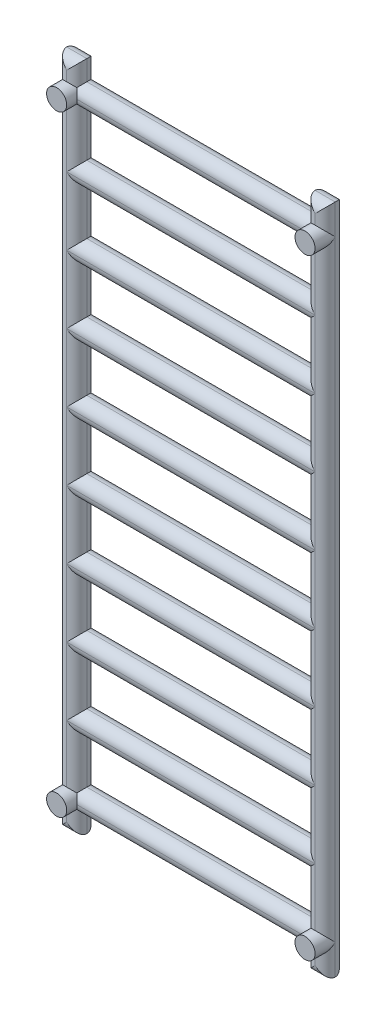
SolidWorks part; units mm, degrees
ref_plane "Спереди" through (0, 0, 0) normal (0, 0, 1) x (1, 0, 0)
ref_plane "Сверху" through (0, 0, 0) normal (0, 1, 0) x (1, 0, 0)
ref_plane "Справа" through (0, 0, 0) normal (1, 0, 0) x (0, 0, -1)
other "Configuration Table"
sketch "Эскиз2" plane through (0, 0, 0) normal (0, 1, 0) x (1, 0, 0)
  line L1 (-15, -15) -> (15, -15)
  line L2 (-15, -15) -> (-15, 15)
  line L3 (-15, 15) -> (15, 15)
  line L4 (15, -15) -> (15, 15)
  line L5 (-15, -15) -> (15, 15) construction
  line L6 (-15, 15) -> (15, -15) construction
  line L7 (355, 15) -> (385, 15)
  line L8 (355, 15) -> (355, -15)
  line L9 (355, -15) -> (385, -15)
  line L10 (385, 15) -> (385, -15)
  line L11 (355, 15) -> (385, -15) construction
  line L12 (355, -15) -> (385, 15) construction
  point P0 (0, 0)
  point P6 (370, 0)
  dimension "D1" = 30
  dimension "D2" = 400
extrude "Бобышка-Вытянуть1" add sketch "Эскиз2" along normal blind 1000
sketch "Эскиз3" plane through (15, 0, 0) normal (1, 0, 0) x (0, 0, -1)
  line L0 (-15, 1000) -> (-15, 0) construction
  line L1 (-15, 60) -> (15, 60)
  line L2 (-15, 60) -> (-15, 30)
  line L3 (-15, 30) -> (15, 30)
  line L4 (15, 60) -> (15, 30)
  line L5 (15, 1000) -> (15, 0) construction
  line L6 (15, 0) -> (15, 30) construction
extrude "Бобышка-Вытянуть2" add sketch "Эскиз3" along normal up to surface (340 mm away) up to face at (355, 500, 0)
pattern_linear "Линейный массив1" count 10 spacing 101.1111 along (0, 1, 0) of "Бобышка-Вытянуть2"
fillet "Скругление1" radius 15 96 edges at (355, 95.5556, -15) (185, 60, -15) (15, 95.5556, -15) (185, 131.1111, -15) (355, 196.6667, -15) (185, 161.1111, -15) (15, 196.6667, -15) (185, 232.2222, -15) (355, 297.7778, -15) (185, 262.2222, -15) (15, 297.7778, -15) (185, 333.3333, -15) (355, 398.8889, -15) (185, 363.3333, -15) (15, 398.8889, -15) (185, 434.4444, -15) (355, 500, -15) (185, 464.4444, -15) (15, 500, -15) (185, 535.5556, -15) (355, 601.1111, -15) (185, 565.5556, -15) (15, 601.1111, -15) (185, 636.6667, -15) (355, 702.2222, -15) (185, 666.6667, -15) (15, 702.2222, -15) (185, 737.7778, -15) (355, 803.3333, -15) (185, 767.7778, -15) (15, 803.3333, -15) (185, 838.8889, -15) (355, 904.4444, -15) (185, 868.8889, -15) (15, 904.4444, -15) (185, 940, -15) (0, 1000, -15) (-15, 500, -15) (0, 0, -15) (15, 15, -15) (185, 30, -15) (355, 15, -15) (370, 0, -15) (385, 500, -15) (370, 1000, -15) (355, 985, -15) (185, 970, -15) (15, 985, -15) (-15, 500, 15) (0, 1000, 15) (15, 985, 15) (185, 970, 15) (355, 985, 15) (370, 1000, 15) (385, 500, 15) (370, 0, 15) (355, 15, 15) (185, 30, 15) (15, 15, 15) (0, 0, 15) (185, 60, 15) (355, 95.5556, 15) (185, 131.1111, 15) (15, 95.5556, 15) (185, 161.1111, 15) (355, 196.6667, 15) (185, 232.2222, 15) (15, 196.6667, 15) (185, 262.2222, 15) (355, 297.7778, 15) (185, 333.3333, 15) (15, 297.7778, 15) (185, 363.3333, 15) (355, 398.8889, 15) (185, 434.4444, 15) (15, 398.8889, 15) (185, 464.4444, 15) (355, 500, 15) (185, 535.5556, 15) (15, 500, 15) (185, 565.5556, 15) (355, 601.1111, 15) (185, 636.6667, 15) (15, 601.1111, 15) (185, 666.6667, 15) (355, 702.2222, 15) (185, 737.7778, 15) (15, 702.2222, 15) (185, 767.7778, 15) (355, 803.3333, 15) (185, 838.8889, 15) (15, 803.3333, 15) (185, 868.8889, 15) (355, 904.4444, 15) (185, 940, 15) (15, 904.4444, 15)
sketch "Эскиз4" plane through (0, 0, 0) normal (0, 0, 1) x (1, 0, 0)
  circle A0 centre (0, 955) radius 15
  circle A1 centre (370, 955) radius 15
  circle A2 centre (370, 45) radius 15
  circle A3 centre (0, 45) radius 15
  dimension "D1" = 30
extrude "Бобышка-Вытянуть3" add sketch "Эскиз4" along normal blind 30
